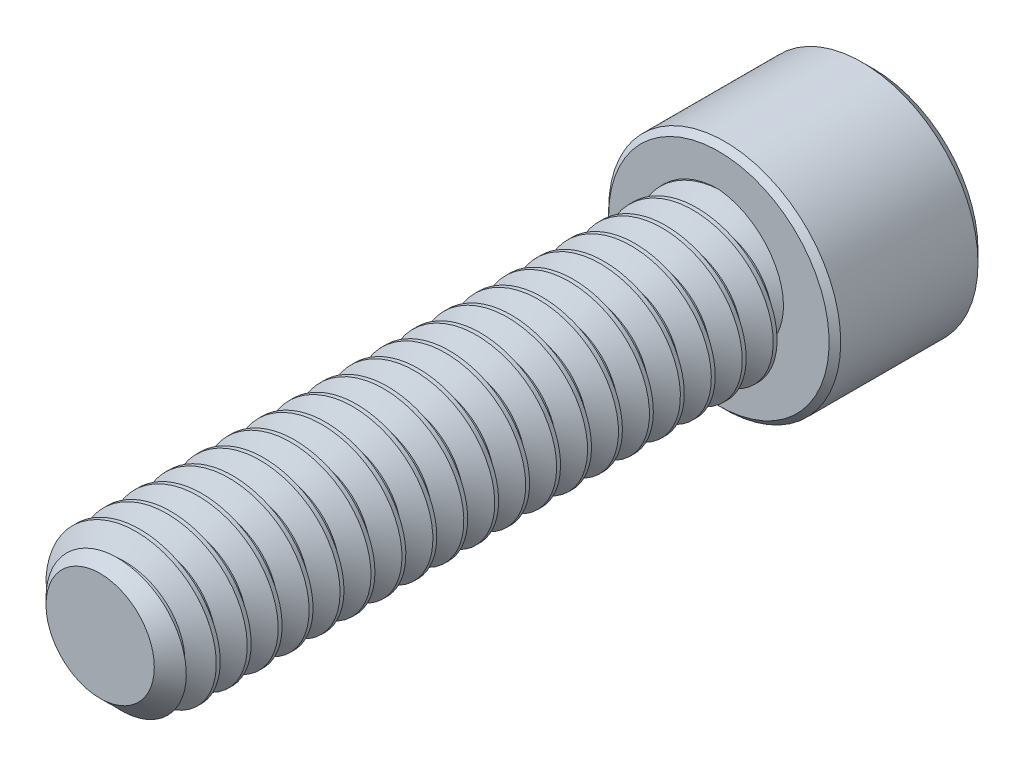
SolidWorks part; units mm, degrees
ref_plane "Front Plane" through (0, 0, 0) normal (0, 0, 1) x (1, 0, 0)
ref_plane "Top Plane" through (0, 0, 0) normal (0, 1, 0) x (1, 0, 0)
ref_plane "Right Plane" through (0, 0, 0) normal (1, 0, 0) x (0, 0, -1)
sketch "Sketch0" plane through (0, 0, 0) normal (1, 0, 0) x (0, 0, -1)
  line L0 (0, 0) -> (25.4, 0) construction
  point P2 (31.75, 0)
  point P4 (0, 0)
  dimension "D1" = 25.4
  dimension "D2" = 6.35
  dimension "Min Thread" = 0
sketch "Sketch1" plane through (0, 0, 0) normal (0, 0, 1) x (1, 0, 0)
  circle A0 centre (0, 0) radius 3.175
  dimension "OD" = 6.35
extrude "Extrude1" add sketch "Sketch1" against normal blind 25.4
sketch "Sketch2" plane through (0, 0, 0) normal (0, 0, 1) x (1, 0, 0)
  circle A0 centre (0, 0) radius 3.175 construction
  circle A1 centre (0, 0) radius 3.175
curve "Helix/Spiral1" pitch 1.27 height 26.67 turns 21 parameters "pitch"=1.27
chamfer "Chamfer3" distance 0.9525 angle 45 1 edges at (3.175, 0, 0)
sketch "Sketch3" plane through (0, 0, 0) normal (1, 0, 0) x (0, 0, -1)
  line L0 (-1.1113, 3.175) -> (-0.635, 2.3501)
  line L1 (-0.635, 2.3501) -> (-0.4763, 2.3501)
  line L2 (-0.4763, 2.3501) -> (0, 3.175)
  line L3 (-1.1113, 3.175) -> (0, 3.175)
  line L4 (-0.5556, 3.175) -> (-0.5556, 2.3501) construction
  line L5 (-0.8731, 2.7626) -> (-0.2381, 2.7626) construction
  line L6 (0, 3.175) -> (0, -3.175) construction
  dimension "D1" = 0.1588
  dimension "D2" = 0.635
  dimension "D3" = 60
sweep "Cut-Sweep1" cut profiles "Sketch3" path "Helix/Spiral1"
sketch "Sketch5" plane through (0, 0, 0) normal (1, 0, 0) x (0, 0, -1)
  line L0 (25.4, -2.3728) -> (25.4, 2.2654) construction
  line L1 (25.4, 3.175) -> (0, 3.175)
  line L2 (25.4, 3.175) -> (25.4, 0)
  line L3 (25.4, 0) -> (-1.1556, 0)
  line L4 (0, 0) -> (25.4, 0) construction
  line L5 (0, 3.175) -> (-1.1556, 0)
  line L6 (0, 0) -> (27.94, 0) construction
  dimension "D1" = 70
  dimension "D3" = 2.54
revolve "partially thread" [suppressed] add sketch "Sketch5" angle 360 about L6
sketch "Sketch6" plane through (0, 0, -25.4) normal (0, 0, -1) x (-1, 0, 0)
  circle A0 centre (0, 0) radius 4.7625
  dimension "head dia" = 9.525
extrude "Extrude2" add sketch "Sketch6" along normal blind 6.35
sketch "Sketch7" plane through (0, 0, -31.75) normal (0, 0, -1) x (-1, 0, 0)
  line L1 (0, 2.7496) -> (-2.3813, 1.3748)
  line L2 (-2.3813, 1.3748) -> (-2.3813, -1.3748)
  line L3 (-2.3813, -1.3748) -> (0, -2.7496)
  line L4 (0, -2.7496) -> (2.3813, -1.3748)
  line L5 (2.3813, -1.3748) -> (2.3813, 1.3748)
  line L6 (2.3813, 1.3748) -> (0, 2.7496)
  circle A0 centre (0, 0) radius 2.3813 construction
  dimension "hex dia" = 4.7625
extrude "Cut-Extrude1" cut sketch "Sketch7" against normal blind 3.5719
sketch "Sketch8" plane through (0, 0, -31.75) normal (0, 0, -1) x (-1, 0, 0)
  circle A0 centre (0, 0) radius 2.7496
extrude "Cut-Extrude2" cut sketch "Sketch8" against normal through all draft 45
chamfer "Chamfer1" distance 0.4763 angle 45 1 edges at (-4.7625, 0, -31.75)
chamfer "Chamfer2" distance 0.2381 angle 45 1 edges at (-4.7625, 0, -25.4)
sketch "Sketch9" plane through (0, 0, 0) normal (1, 0, 0) x (0, 0, -1)
  line L0 (0, 3.175) -> (0, -3.175) construction
  line L1 (3.175, 3.175) -> (3.175, -3.175) construction
  line L2 (31.75, 4.7625) -> (31.75, -4.7625) construction
  line L3 (25.4, 4.7625) -> (25.4, -4.7625) construction
  line L4 (25.4, 4.5244) -> (25.4, -4.5244) construction
  line L5 (31.75, -4.2863) -> (31.75, 4.2863) construction
  line L6 (25.4, -4.7625) -> (25.4, 4.7625) construction
  line L7 (0, 2.2225) -> (0, -2.2225) construction
  line L8 (-1.1113, 3.175) -> (0, 3.175) construction
  line L9 (3.175, 0) -> (0, 0) construction
  dimension "D1" = 3.175
equation "\"D3@Helix/Spiral1\" = \"screw length@Extrude1\"+\"pitch@Helix/Spiral1\""
equation "\"D1@Sketch3\" = \"pitch@Helix/Spiral1\"*.125"
equation "\"D2@Sketch3\" = \"pitch@Helix/Spiral1\"*.5"
equation "\"D1@Cut-Extrude1\" = \"hex dia@Sketch7\"*.75"
equation "\"D1@Chamfer1\" = \"head dia@Sketch6\"*.05"
equation "\"D1@Sketch9\" = \"pitch@Helix/Spiral1\"*2.50"
equation "\"D1@Chamfer2\" = \"D1@Chamfer1\"/2"
equation "\"D1@Chamfer3\" = \"pitch@Helix/Spiral1\"*.750"
equation "\"D1@Sketch0\" = \"screw length@Extrude1\""
equation "\"D2@Sketch0\" = \"head depth@Extrude2\""
